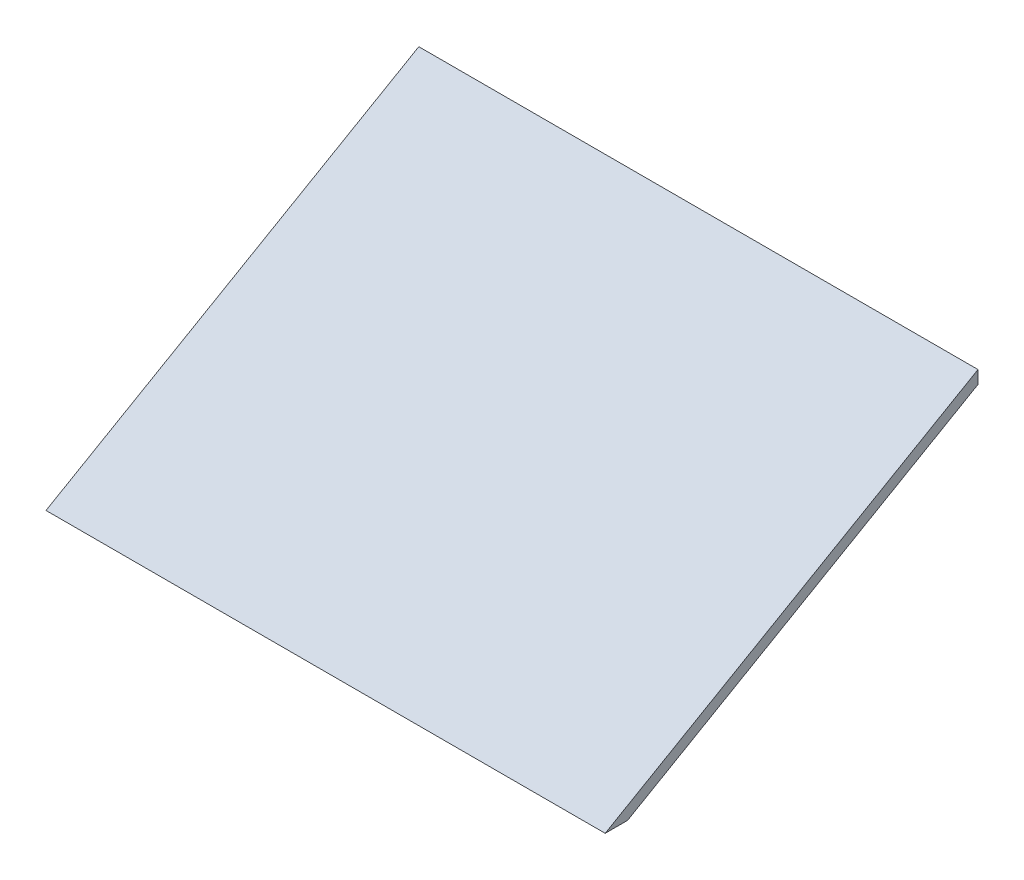
SolidWorks part; units mm, degrees
ref_plane "Front Plane" through (0, 0, 0) normal (0, 0, 1) x (1, 0, 0)
ref_plane "Top Plane" through (0, 0, 0) normal (0, 1, 0) x (1, 0, 0)
ref_plane "Right Plane" through (0, 0, 0) normal (1, 0, 0) x (0, 0, -1)
sketch "Sketch1" plane through (0, 0, 0) normal (1, 0, 0) x (0, 0, -1)
  line L0 (0, 0) -> (-94, -54.2709)
  line L1 (-94, -54.2709) -> (-100, -54.2709)
  line L2 (-100, -54.2709) -> (0, 3.4641)
  line L3 (0, 3.4641) -> (0, 0)
  dimension "D1" = 100
  dimension "D2" = 30
  dimension "D3" = 3
extrude "Boss-Extrude1" add sketch "Sketch1" along normal blind 150
